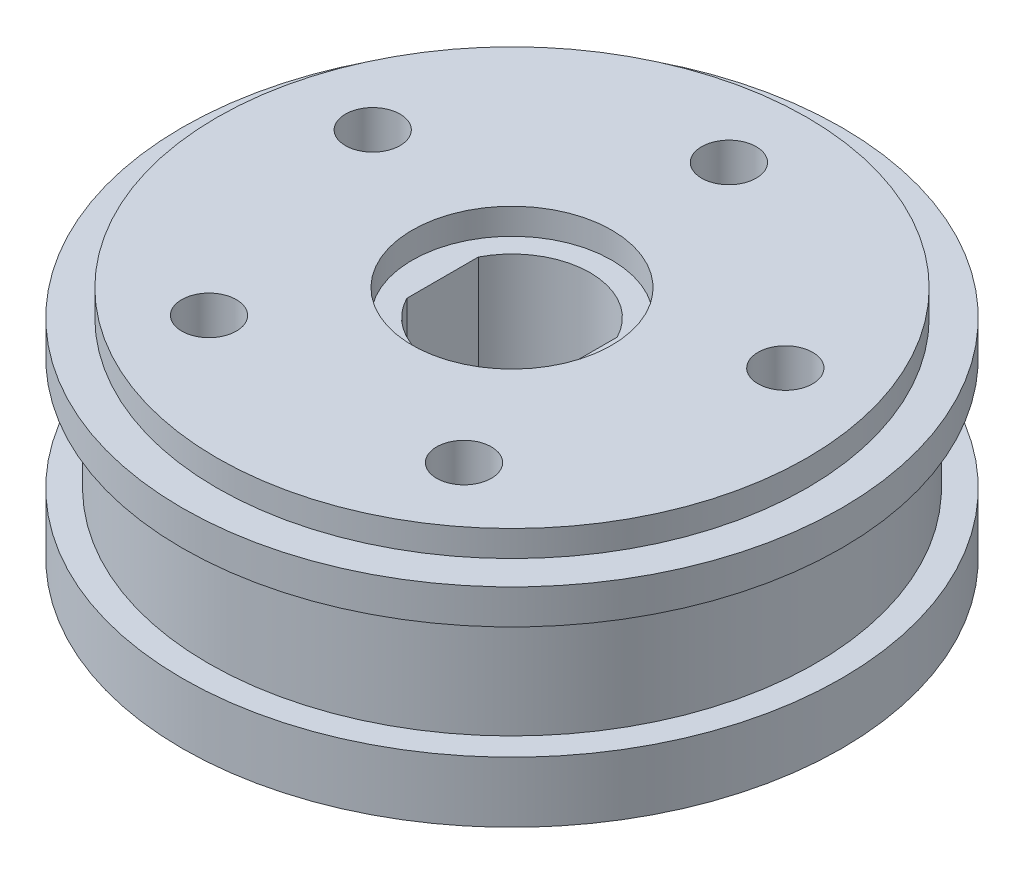
SolidWorks part; units mm, degrees
material "PA Type 6"
ref_plane "Front Plane" through (0, 0, 0) normal (0, 0, 1) x (1, 0, 0)
ref_plane "Top Plane" through (0, 0, 0) normal (0, 1, 0) x (1, 0, 0)
ref_plane "Right Plane" through (0, 0, 0) normal (1, 0, 0) x (0, 0, -1)
sketch "Sketch1" plane through (0, 0, 0) normal (0, 0, 1) x (1, 0, 0)
  line L0 (0, 0) -> (19, 0)
  line L1 (19, 0) -> (19, 3.5)
  line L2 (19, 3.5) -> (17.5, 3.5)
  line L3 (17.5, 3.5) -> (17.5, 10)
  line L4 (17.5, 10) -> (19, 10)
  line L5 (19, 10) -> (19, 13.5)
  line L6 (19, 13.5) -> (0, 13.5)
  line L7 (0, 13.5) -> (0, 0)
  dimension "D1" = 17.5
  dimension "D2" = 13.5
  dimension "D3" = 1.5
  dimension "D4" = 6.5
revolve "Revolve1" add sketch "Sketch1" angle 360 about L7
sketch "Sketch4" plane through (0, 13.5, 0) normal (0, 1, 0) x (1, 0, 0)
  point P0 (0, 0)
hole_wizard "Ø9.0 (9) Diameter Hole1" positions "Sketch4" profile "Sketch5" hole size "Ø9.0" standard "DIN" end condition through all
sketch "Sketch5" plane through (0, 13.5, 0) normal (1, 0, 0) x (0, 0, 1)
  line L0 (0, 0) -> (0, 13.5)
  line L1 (0, 13.5) -> (4.5, 13.5)
  line L2 (4.5, 13.5) -> (4.5, 0)
  line L5 (4.5, 0) -> (0, 0)
  line L11 (0, -6.35) -> (0, 107.95) construction
  dimension "Thru Hole Dia." = 9
  dimension "Thru Hole Depth" = 13.5
sketch "Sketch6" plane through (0, 13.5, 0) normal (0, 1, 0) x (1, 0, 0)
  circle A0 centre (0, 0) radius 5.75
  dimension "D1" = 11.5
extrude "Cut-Extrude1" cut sketch "Sketch6" against normal blind 1.5 and the other way through all
extrude "Cut-Extrude2" cut sketch "Sketch6<2>" along normal blind 1.5 from surface starting at face at (0, 0, 4.5)
sketch "Sketch6<2>" plane through (0, 13.5, 0) normal (0, 1, 0) x (1, 0, 0) same geometry as "Sketch6"
sketch "Sketch7" plane through (0, 12, 0) normal (0, 1, 0) x (1, 0, 0)
  line L1 (4, -2.0616) -> (-4, -2.0616)
  line L2 (4, -2.0616) -> (4, 2.0616)
  line L3 (4, 2.0616) -> (-4, 2.0616)
  line L4 (-4, -2.0616) -> (-4, 2.0616)
  circle A0 centre (0, 0) radius 4.5 construction
  circle A1 centre (0, 0) radius 4.5
  point P6 (0, 0)
  point P8 (4, 0)
  circle M7 centre (0, 0) radius 4.5
  dimension "D1" = 8
extrude "Boss-Extrude1" add sketch "Sketch7" along direction (0, 1, 0) on the side against the normal up to surface (10.5 mm away) contours L4 M7 | L2 M7 region at (4.201, 12, 0) region at (-4.201, 12, 0) up to face at (0, 1.5, 5.75)
sketch "Sketch10" plane through (0, 13.5, 0) normal (0, 1, 0) x (1, 0, 0)
  circle A0 centre (0, 0) radius 12.5
  point P4 (0, 12.5)
  point P11 (11.8882, 3.8627)
  point P12 (7.3473, -10.1127)
  point P13 (-7.3473, -10.1127)
  point P14 (-11.8882, 3.8627)
  dimension "D1" = 25
  dimension "D2" = 5
hole_wizard "Tap Drill for M3 Helicoil1" positions "Sketch10" profile "Sketch9" hole size "M3x0.5" standard "DIN" end condition through all
sketch "Sketch9" plane through (-11.8882, 13.5, -3.8627) normal (1, 0, 0) x (0, 0, 1)
  line L0 (0, 0) -> (0, 13.5)
  line L1 (0, 13.5) -> (1.575, 13.5)
  line L2 (1.575, 13.5) -> (1.575, 0)
  line L5 (1.575, 0) -> (0, 0)
  line L11 (0, -6.35) -> (0, 107.95) construction
  dimension "Thru Hole Dia." = 3.15
  dimension "Thru Hole Depth" = 13.5
sketch "Sketch11" plane through (0, 13.5, 0) normal (0, 1, 0) x (1, 0, 0)
  circle A0 centre (0, 0) radius 19 construction
  circle A1 centre (0, 0) radius 19
  circle A2 centre (0, 0) radius 17
  dimension "D1" = 2
extrude "Cut-Extrude3" cut sketch "Sketch11" against normal blind 1.5
